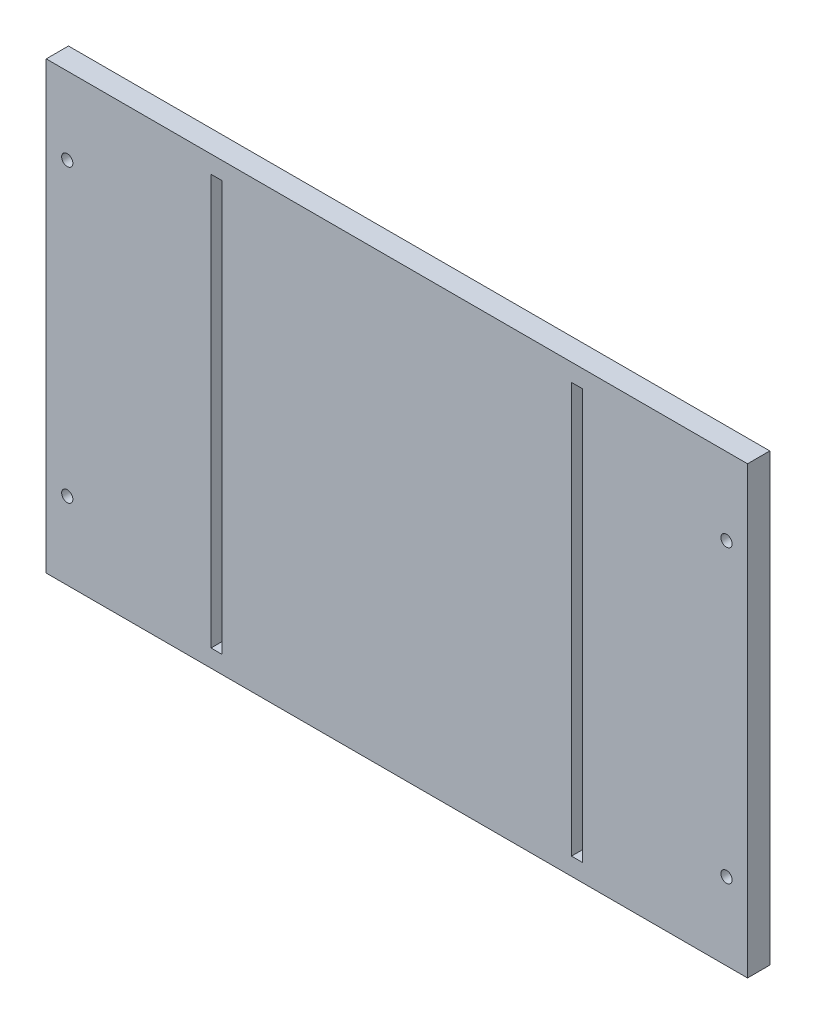
SolidWorks part; units mm, degrees
ref_plane "Front Plane" through (0, 0, 0) normal (0, 0, 1) x (1, 0, 0)
ref_plane "Top Plane" through (0, 0, 0) normal (0, 1, 0) x (1, 0, 0)
ref_plane "Right Plane" through (0, 0, 0) normal (1, 0, 0) x (0, 0, -1)
sketch "Sketch1" plane through (0, 0, 0) normal (0, 0, 1) x (1, 0, 0)
  line L0 (100, 127) -> (100, 0) construction
  line L1 (0, 0) -> (200, 0)
  line L2 (0, 0) -> (0, 127)
  line L3 (0, 127) -> (200, 127)
  line L4 (200, 0) -> (200, 127)
  line L5 (0, 63.5) -> (200, 63.5) construction
  circle A3 centre (6, 105) radius 1.6
  circle A7 centre (194, 105) radius 1.6
  circle A8 centre (194, 22) radius 1.6
  circle A9 centre (6, 22) radius 1.6
  dimension "D11" = 3.2
  dimension "D1" = 127
  dimension "D2" = 200
  dimension "D12" = 6
  dimension "D13" = 22
extrude "Wall" add sketch "Sketch1" along normal blind 6.35
sketch "Sketch2" [suppressed] plane through (0, 0, 6.35) normal (0, 0, 1) x (1, 0, 0)
  line L0 (135.35, 127) -> (135.35, 98.425) construction
  line L1 (270.7, 127) -> (0, 127) construction
  line L2 (135.35, 98.425) -> (66.6667, 98.425) construction
  line L3 (135.35, 98.425) -> (204.0333, 98.425) construction
  line L4 (0, 127) -> (0, 0) construction
  circle A0 centre (135.35, 98.425) radius 3.9687
  circle A1 centre (66.6667, 98.425) radius 3.9688
  circle A2 centre (204.0333, 98.425) radius 3.9687
  dimension "D2" = 7.9375
  dimension "D1" = 28.575
  dimension "D3" = 66.6667
extrude "RodSupportCutouts" [suppressed] cut sketch "Sketch2" against normal up to next
sketch "Sketch3" [suppressed] plane through (0, 0, 6.35) normal (0, 0, 1) x (1, 0, 0)
  line L1 (25.4, 88.9) -> (245.3, 88.9)
  line L2 (25.4, 88.9) -> (25.4, 114.3)
  line L3 (25.4, 114.3) -> (245.3, 114.3)
  line L4 (245.3, 88.9) -> (245.3, 114.3)
  line L5 (25.4, 88.9) -> (245.3, 114.3) construction
  line L6 (25.4, 114.3) -> (245.3, 88.9) construction
  line L7 (270.7, 127) -> (0, 127) construction
  line L8 (0, 127) -> (0, 0) construction
  point P0 (135.35, 101.6)
  point P9 (135.35, 127)
  dimension "D1" = 25.4
  dimension "D2" = 25.4
  dimension "D3" = 25.4
extrude "CannulaLargeCutout" [suppressed] cut sketch "Sketch3" against normal up to next
sketch "Sketch4" [suppressed] plane through (0, 0, 9.525) normal (0, 0, 1) x (1, 0, 0)
  line L0 (6, 103.5) -> (194, 103.5) construction
  line L1 (6, 105) -> (6, 22) construction
  line L2 (194, 105) -> (194, 22) construction
  line L3 (200, 127) -> (0, 127) construction
  line L4 (0, 127) -> (0, 0) construction
  circle A0 centre (60, 103.5) radius 6.35
  circle A1 centre (20, 103.5) radius 6.35
  circle A2 centre (100, 103.5) radius 6.35
  circle A3 centre (140, 103.5) radius 6.35
  circle A4 centre (60, 63.5) radius 6.35
  circle A5 centre (100, 63.5) radius 6.35
  circle A6 centre (140, 63.5) radius 6.35
  circle A7 centre (60, 23.5) radius 6.35
  circle A8 centre (100, 23.5) radius 6.35
  circle A9 centre (140, 23.5) radius 6.35
  circle A10 centre (20, 63.5) radius 6.35
  circle A11 centre (20, 23.5) radius 6.35
  circle A12 centre (180, 103.5) radius 6.35
  circle A13 centre (180, 63.5) radius 6.35
  circle A14 centre (180, 23.5) radius 6.35
  point P42 (100, 127)
  point P45 (0, 63.5)
  dimension "D3" = 12.7
  dimension "D1" = 5
  dimension "D2" = 3
extrude "CannulaHoles" [suppressed] cut sketch "Sketch4" against normal up to next
ref_plane "LeftBoundary" [suppressed] through (25.4, 0, 0) normal (-1, 0, 0) x (0, 0, 1)
ref_plane "RightBoundary" [suppressed] through (245.3, 0, 0) normal (1, 0, 0) x (0, 0, -1)
ref_plane "TopBoundary" [suppressed] through (0, 101.6, 0) normal (0, 1, 0) x (1, 0, 0)
ref_plane "BottomBoundary" [suppressed] through (0, 25.4, 0) normal (0, -1, 0) x (-1, 0, 0)
sketch "Sketch5" [suppressed] plane through (0, 0, 6.35) normal (0, 0, 1) x (1, 0, 0)
  line L4 (25.4, 3.4925) -> (25.4, -3.4925) construction
  line L5 (3.4925, 101.6) -> (-3.4925, 101.6) construction
  circle A0 centre (25.4, 101.6) radius 3.9687
  dimension "D1" = 7.9375
extrude "RodSupportCutout" [suppressed] cut sketch "Sketch5" along normal blind 3.35 from surface starting at face at (4.4, 22, 0)
pattern_linear "SupportPattern" [suppressed] count 7 spacing 36.65 count 5 spacing 19.05 of bodies 105
sketch "Sketch6" plane through (0, 0, 6.35) normal (0, 0, 1) x (1, 0, 0)
  line L0 (47, 122) -> (50.2, 122)
  line L1 (149.8, 122) -> (153, 122)
  line L2 (149.8, 122) -> (149.8, 5)
  line L3 (149.8, 5) -> (153, 5)
  line L4 (153, 122) -> (153, 5)
  line L5 (47, 122) -> (47, 5)
  line L6 (47, 5) -> (50.2, 5)
  line L7 (50.2, 122) -> (50.2, 5)
  line L8 (0, 127) -> (0, 0) construction
  line L9 (0, 0) -> (200, 0) construction
  line L10 (200, 0) -> (200, 127) construction
  line L11 (0, 0) -> (200, 0) construction
  point P7 (200, 57)
  dimension "D1" = 117
  dimension "D2" = 5
  dimension "SlitDiameter" = 3.2
  dimension "D4" = 47
  dimension "D5" = 47
  dimension "D6" = 5
  dimension "D7" = 117
  dimension "D3" = 3.2
extrude "Cut-Extrude1" cut sketch "Sketch6" against normal through all
equation "\"Length\"= 283mm"
equation "\"Width\"= 225mm"
equation "\"WallThickness\"= 0.25in"
equation "\"UpperWaterJacketThickness\"= 28mm"
equation "\"SpacerHeight\"= 80.2mm"
equation "\"SpacerCornerWidth\"= 10mm"
equation "\"SpacerCornerHeight\"= 60.16mm"
equation "\"SpacerPegDiameter\"= 10mm"
equation "\"SpacerPegHeight\"= 10mm"
equation "\"TubingShort\"= 110mm"
equation "\"TubingLong\"= 175mm"
equation "\"PlateLength\"= 252mm"
equation "\"PlateWidth\"= 190mm"
equation "\"PlateHoleDiameter\"= 5.9mm"
equation "\"PlateHoleBottom\"= 2mm"
equation "\"PlateHoleSide\"= 1.55mm"
equation "\"PlateHoleSpacing\"= 3.1mm"
equation "\"PlateThickness\"= 1.55mm"
equation "\"ReservoirBottom\"= 12.5mm"
equation "\"ReservoirSupportWidth\"= 12mm"
equation "\"ReservoirSupportHeight\"= 15.1mm"
equation "\"ReservoirSupportPlacementHeight\"= 50mm"
equation "\"ReservoirHoleDiameter\"= 12.7mm"
equation "\"ReservoirHoleRight\"= 25mm"
equation "\"ReservoirHoleTop\"= \"ReservoirSupportPlacementHeight\""
equation "\"ReservoirHeight\"= 90mm"
equation "\"ReservoirPortBottom\"= 4mm"
equation "\"ReservoirPortTop\"= 10mm"
equation "\"ReservoirPortWidth\"= 101mm"
equation "\"CustomSpacerHeight\"= 5in"
equation "\"CustomSpacerRodHoleHeight\"= .75in"
equation "\"CustomSpacerRodHoleDiameter\"= .3125in"
equation "\"ScrewBlockSide\"= 12mm"
equation "\"ScrewBlockUpperHeight\"= 16mm"
equation "\"ScrewBlockLowerHeight\"= 16mm"
equation "\"InternalLength\"= 258mm"
equation "\"InternalWidth\"= 200mm"
equation "\"CustomSpacerPegHeight\"= 1in"
equation "\"CustomSpacerScrewBore\"=3.2mm"
equation "\"CustomSpacerScrewDepth\"=10mm"
equation "\"D1@Sketch1\"=\"CustomSpacerHeight\""
equation "\"D2@Sketch1\"=\"WallLength\""
equation "\"D11@Sketch1\"=\"CustomSpacerScrewBore\""
equation "\"D12@Sketch1\"   = \"ScrewBlockSide\"/2"
equation "\"D13@Sketch1\"=\"ScrewBlockUpperHeight\"+\"ScrewBlockSide\"/2"
equation "\"D1@Wall\" = \"WallThickness\""
equation "\"D1@Sketch2\"=\"CustomSpacerRodHoleHeight\" + \"CustomSpacerRodHoleDiameter\" +0.0625in"
equation "\"D2@Sketch2\"=\"CustomSpacerRodHoleDiameter\""
equation "\"D3@Sketch2\"=\"InternalWidth\" / 3"
equation "\"D1@Sketch3\"=1in"
equation "\"WallLength\"= \"InternalWidth\""
equation "\"D1@Sketch5\"=\"CustomSpacerRodHoleDiameter\""
equation "\"D1@RodSupportCutout\"      = \"WallThickness\" - 3"
equation "\"SlitDiameter@Sketch6\" = \"CustomSpacerScrewBore\""
equation "\"D3@Sketch6\"=\"CustomSpacerScrewBore\""
